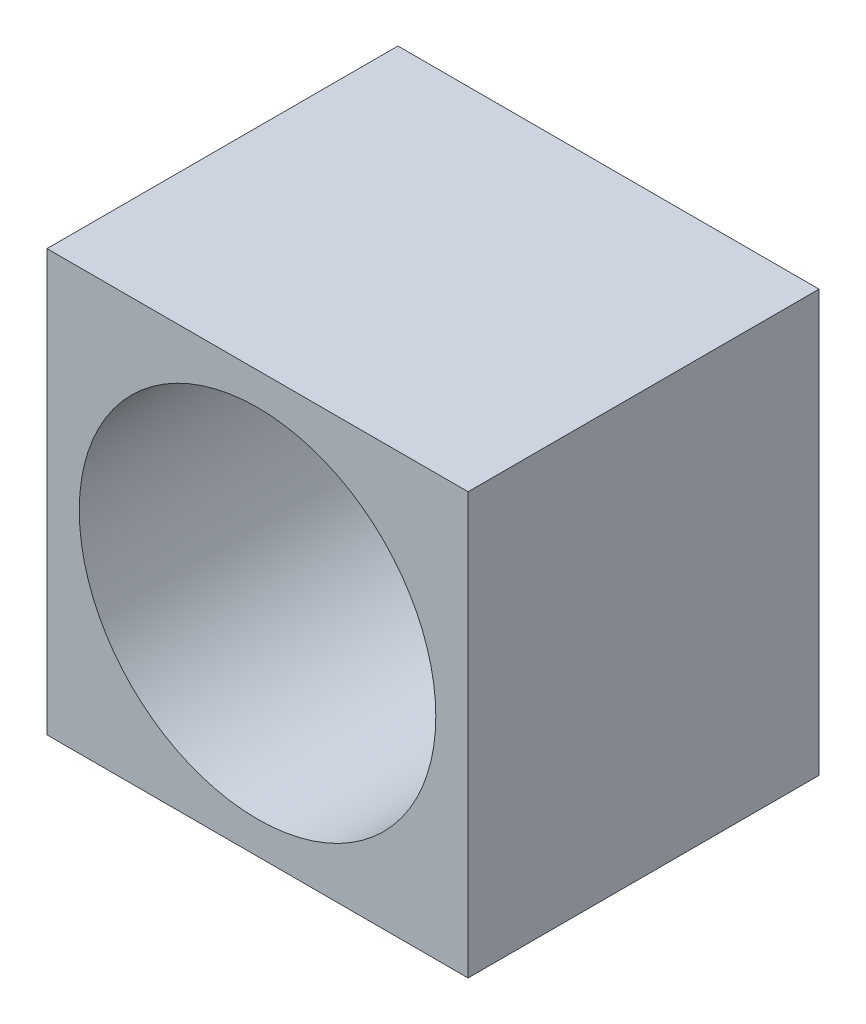
SolidWorks part; units mm, degrees
ref_plane "Front Plane" through (0, 0, 0) normal (0, 0, 1) x (1, 0, 0)
ref_plane "Top Plane" through (0, 0, 0) normal (0, 1, 0) x (1, 0, 0)
ref_plane "Right Plane" through (0, 0, 0) normal (1, 0, 0) x (0, 0, -1)
sketch "Sketch1" plane through (0, 0, 0) normal (0, 1, 0) x (1, 0, 0)
  line L0 (-15, -12.5) -> (15, -12.5)
  line L1 (0, 0) -> (15, 0) construction
  line L2 (0, 0) -> (0, 12.5) construction
  line L3 (-15, 12.5) -> (15, 12.5)
  line L4 (15, -12.5) -> (15, 12.5)
  line L5 (-15, -12.5) -> (-15, 12.5)
  point P8 (0, -12.5)
  dimension "D1" = 12.5
  dimension "D2" = 15
extrude "Boss-Extrude1" add sketch "Sketch1" along normal blind 15 and the other way blind 15
sketch "Sketch2" plane through (0, 0, 12.5) normal (0, 0, 1) x (1, 0, 0)
  circle A0 centre (0, 0) radius 12.5 construction
  circle A1 centre (0, 0) radius 12.7
  dimension "D1" = 25
  dimension "D2" = 0.2
extrude "Cut-Extrude1" cut sketch "Sketch2" against normal through all
